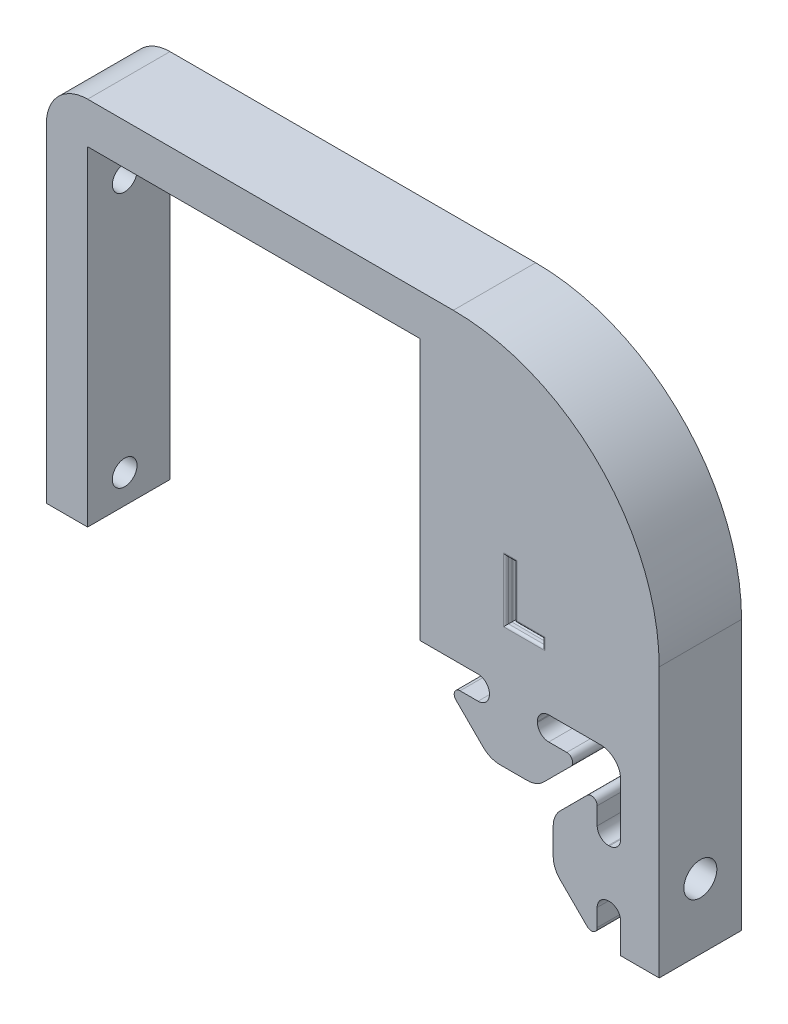
SolidWorks part; units mm, degrees
ref_plane "Front Plane" through (0, 0, 0) normal (0, 0, 1) x (1, 0, 0)
ref_plane "Top Plane" through (0, 0, 0) normal (0, 1, 0) x (1, 0, 0)
ref_plane "Right Plane" through (0, 0, 0) normal (1, 0, 0) x (0, 0, -1)
sketch "Sketch1" plane through (0, 0, 0) normal (0, 0, 1) x (1, 0, 0)
  line L0 (13.02, -7.9417) -> (17.7, -7.9417)
  line L1 (17.7, -7.9417) -> (17.7, 49.77)
  line L2 (17.7, 49.77) -> (-56.7, 49.77)
  line L3 (-14.4742, 2.77) -> (-67.0037, 2.77) construction
  line L4 (-19.4439, 2.77) -> (-19.4439, 44.77) construction
  line L5 (-10.5664, 13.02) -> (-10.5664, 44.77)
  line L6 (-10.5664, 44.77) -> (-51.7, 44.77)
  line L7 (-51.7, 44.77) -> (-51.7, 4.77)
  line L8 (-56.7, 49.77) -> (-56.7, 4.77)
  line L9 (-56.7, 4.77) -> (-51.7, 4.77)
  line L10 (12.7, -6.3331) -> (12.7, -7.9417) construction
  line L11 (13.02, -5.3171) -> (13.02, -4.2875)
  line L12 (11.651, -2.9185) -> (11.5392, -2.9185)
  line L13 (10.1702, -4.2875) -> (10.1702, -6.4021)
  line L14 (8.9631, -6.9029) -> (5.667, -3.6143)
  line L15 (4.8285, -1.5932) -> (4.8285, 1.5932)
  line L16 (5.667, 3.6143) -> (8.9631, 6.9029)
  line L17 (10.1702, 6.4021) -> (10.1702, 4.2875)
  line L18 (11.5392, 2.9185) -> (11.651, 2.9185)
  line L19 (13.02, 10.5773) -> (13.02, 4.2875)
  line L20 (6.3329, 13.02) -> (10.5626, 13.0198)
  line L22 (6.3329, 13.02) -> (4.2875, 13.02)
  line L23 (2.9185, 11.651) -> (2.9185, 11.5392)
  line L24 (4.2875, 10.1702) -> (6.4768, 10.1702)
  line L25 (6.981, 8.9509) -> (3.6723, 5.6497)
  line L26 (1.6558, 4.8158) -> (-1.6558, 4.8158)
  line L27 (-3.6723, 5.6497) -> (-6.981, 8.9509)
  line L28 (-6.4768, 10.1702) -> (-4.2875, 10.1702)
  line L29 (-2.9185, 11.5392) -> (-2.9185, 11.651)
  line L30 (-4.2875, 13.02) -> (-5.3171, 13.02)
  line L31 (-5.3171, 13.02) -> (-10.5664, 13.02)
  line L32 (13.02, -5.3171) -> (13.02, -7.9417)
  line L33 (13.02, -6.3331) -> (13.02, -7.9417) construction
  line L34 (13.02, 4.2875) -> (13.02, 5.3171) construction
  line L37 (5.3171, 13.02) -> (4.2875, 13.02) construction
  line L38 (-6.3331, 13.02) -> (-9.5504, 13.02) construction
  line L96 (12.7, -5.3171) -> (12.7, -4.2875) construction
  line L97 (11.651, -3.2385) -> (11.5392, -3.2385) construction
  line L98 (10.4902, -4.2875) -> (10.4902, -6.4021) construction
  line L99 (8.7371, -7.1294) -> (5.441, -3.8408) construction
  line L100 (4.5085, -1.5932) -> (4.5085, 1.5932) construction
  line L101 (5.441, 3.8408) -> (8.7371, 7.1294) construction
  line L102 (10.4902, 6.4021) -> (10.4902, 4.2875) construction
  line L103 (11.5392, 3.2385) -> (11.651, 3.2385) construction
  line L104 (12.7, 4.2875) -> (12.7, 5.3171) construction
  line L105 (12.7, 6.3331) -> (12.7, 9.5504) construction
  line L106 (9.5504, 12.7) -> (6.3331, 12.7) construction
  line L107 (5.3171, 12.7) -> (4.2875, 12.7) construction
  line L108 (3.2385, 11.651) -> (3.2385, 11.5392) construction
  line L109 (4.2875, 10.4902) -> (6.4768, 10.4902) construction
  line L110 (7.207, 8.7244) -> (3.8983, 5.4232) construction
  line L111 (1.6558, 4.4958) -> (-1.6558, 4.4958) construction
  line L112 (-3.8983, 5.4232) -> (-7.207, 8.7244) construction
  line L113 (-6.4768, 10.4902) -> (-4.2875, 10.4902) construction
  line L114 (-3.2385, 11.5392) -> (-3.2385, 11.651) construction
  line L115 (-4.2875, 12.7) -> (-5.3171, 12.7) construction
  line L116 (-6.3331, 12.7) -> (-9.5504, 12.7) construction
  arc A0 (13.02, -4.2875) -> (11.651, -2.9185) centre (11.651, -4.2875) ccw
  arc A1 (11.5392, -2.9185) -> (10.1702, -4.2875) centre (11.5392, -4.2875) ccw
  arc A2 (8.9631, -6.9029) -> (10.1702, -6.4021) centre (9.4628, -6.4021) ccw
  arc A3 (4.8285, -1.5932) -> (5.667, -3.6143) centre (7.6835, -1.5932) ccw
  arc A4 (5.667, 3.6143) -> (4.8285, 1.5932) centre (7.6835, 1.5932) ccw
  arc A5 (10.1702, 6.4021) -> (8.9631, 6.9029) centre (9.4628, 6.4021) ccw
  arc A6 (10.1702, 4.2875) -> (11.5392, 2.9185) centre (11.5392, 4.2875) ccw
  arc A7 (11.651, 2.9185) -> (13.02, 4.2875) centre (11.651, 4.2875) ccw
  arc A8 (4.2875, 13.02) -> (2.9185, 11.651) centre (4.2875, 11.651) ccw
  arc A9 (2.9185, 11.5392) -> (4.2875, 10.1702) centre (4.2875, 11.5392) ccw
  arc A10 (6.981, 8.9509) -> (6.4768, 10.1702) centre (6.4768, 9.4563) ccw
  arc A11 (1.6558, 4.8158) -> (3.6723, 5.6497) centre (1.6558, 7.6708) ccw
  arc A12 (-3.6723, 5.6497) -> (-1.6558, 4.8158) centre (-1.6558, 7.6708) ccw
  arc A13 (-6.4768, 10.1702) -> (-6.981, 8.9509) centre (-6.4768, 9.4563) ccw
  arc A14 (-4.2875, 10.1702) -> (-2.9185, 11.5392) centre (-4.2875, 11.5392) ccw
  arc A15 (-2.9185, 11.651) -> (-4.2875, 13.02) centre (-4.2875, 11.651) ccw
  arc A16 (13.02, 10.5773) -> (10.5626, 13.0198) centre (10.5918, 10.5918) ccw
  arc A17 (13.0198, 10.5625) -> (10.5626, 13.0198) centre (10.5918, 10.5918) ccw construction
  arc A114 (12.7, -5.3171) -> (12.7, -6.3331) centre (12.7, -5.8251) ccw construction
  arc A115 (12.7, -4.2875) -> (11.651, -3.2385) centre (11.651, -4.2875) ccw construction
  arc A116 (11.5392, -3.2385) -> (10.4902, -4.2875) centre (11.5392, -4.2875) ccw construction
  arc A117 (8.7371, -7.1294) -> (10.4902, -6.4021) centre (9.4628, -6.4021) ccw construction
  arc A118 (4.5085, -1.5932) -> (5.441, -3.8408) centre (7.6835, -1.5932) ccw construction
  arc A119 (5.441, 3.8408) -> (4.5085, 1.5932) centre (7.6835, 1.5932) ccw construction
  arc A120 (10.4902, 6.4021) -> (8.7371, 7.1294) centre (9.4628, 6.4021) ccw construction
  arc A121 (10.4902, 4.2875) -> (11.5392, 3.2385) centre (11.5392, 4.2875) ccw construction
  arc A122 (11.651, 3.2385) -> (12.7, 4.2875) centre (11.651, 4.2875) ccw construction
  arc A123 (12.7, 6.3331) -> (12.7, 5.3171) centre (12.7, 5.8251) ccw construction
  arc A124 (12.6998, 10.5664) -> (12.7, 9.5504) centre (12.7, 10.0584) ccw construction
  arc A125 (12.6998, 10.5664) -> (10.5664, 12.6998) centre (10.5918, 10.5918) ccw construction
  arc A126 (9.5504, 12.7) -> (10.5664, 12.6998) centre (10.0584, 12.7) ccw construction
  arc A127 (5.3171, 12.7) -> (6.3331, 12.7) centre (5.8251, 12.7) ccw construction
  arc A128 (4.2875, 12.7) -> (3.2385, 11.651) centre (4.2875, 11.651) ccw construction
  arc A129 (3.2385, 11.5392) -> (4.2875, 10.4902) centre (4.2875, 11.5392) ccw construction
  arc A130 (7.207, 8.7244) -> (6.4768, 10.4902) centre (6.4768, 9.4563) ccw construction
  arc A131 (1.6558, 4.4958) -> (3.8983, 5.4232) centre (1.6558, 7.6708) ccw construction
  arc A132 (-3.8983, 5.4232) -> (-1.6558, 4.4958) centre (-1.6558, 7.6708) ccw construction
  arc A133 (-6.4768, 10.4902) -> (-7.207, 8.7244) centre (-6.4768, 9.4563) ccw construction
  arc A134 (-4.2875, 10.4902) -> (-3.2385, 11.5392) centre (-4.2875, 11.5392) ccw construction
  arc A135 (-3.2385, 11.651) -> (-4.2875, 12.7) centre (-4.2875, 11.651) ccw construction
  arc A136 (-6.3331, 12.7) -> (-5.3171, 12.7) centre (-5.8251, 12.7) ccw construction
  arc A137 (-10.5664, 12.6998) -> (-9.5504, 12.7) centre (-10.0584, 12.7) ccw construction
  dimension "D1" = 47
  dimension "D2" = 74.4
  dimension "D3" = 5
  dimension "D4" = 5
  dimension "D5" = 40
  dimension "D6" = 5
  dimension "D8" = 0.32
  dimension "D7" = 6.2898
  dimension "D9" = 4.2297
  dimension "D11" = 57.7117
extrude "Boss-Extrude1" add sketch "Sketch1" along normal blind 10
sketch "Sketch2" plane through (-56.7, 0, 0) normal (-1, 0, 0) x (0, 0, 1)
  line L1 (10, 49.77) -> (0, 49.77) construction
  line L2 (10, 29.3002) -> (10, 4.77) construction
  line L7 (5.5, 39.27) -> (5.5, 8.27) construction
  circle A0 centre (5.5, 8.27) radius 1.5
  circle A1 centre (5.5, 39.27) radius 1.5
  dimension "D3" = 3
  dimension "D4" = 3
  dimension "D1" = 4.5
  dimension "D2" = 31
  dimension "D5" = 10.5
extrude "Cut-Extrude1" cut sketch "Sketch2" against normal up to next
fillet "Fillet3" radius 5 1 edges at (-56.7, 49.77, 5)
sketch "Sketch3" plane through (17.7, 0, 0) normal (1, 0, 0) x (0, 0, -1)
  line L0 (-5, 1.5932) -> (-5, -1.5932) construction
  line L1 (-10, 0) -> (0, 0) construction
  line L4 (0, -1.5932) -> (0, 1.5932)
  line L5 (-10, -1.5932) -> (0, -1.5932)
  line L6 (-10, 1.5932) -> (-10, -1.5932)
  line L7 (0, 1.5932) -> (-10, 1.5932)
  line L12 (0, -1.5932) -> (0, 1.5932) construction
  line L13 (-10, -1.5932) -> (0, -1.5932) construction
  line L14 (-10, 1.5932) -> (-10, -1.5932) construction
  line L15 (0, 1.5932) -> (-10, 1.5932) construction
  circle A2 centre (-5, 0) radius 2
  dimension "D1" = 0
extrude "Cut-Extrude2" cut sketch "Sketch3" against normal up to next contours A2
fillet "Fillet4" radius 25 1 edges at (17.7, 49.77, 5)
sketch "Sketch7" plane through (0, 0, 10) normal (0, 0, 1) x (1, 0, 0)
  text T0 "L" font "Arial" height in points 28
extrude "Cut-Extrude7" cut sketch "Sketch7" against normal blind 1
fillet "Fillet8" radius 0.3 12 edges at (-0.901, 23.4386, 9) (-0.3939, 27.0343, 9) (0.1132, 23.8535, 9) (1.8188, 20.6728, 9) (3.5244, 20.2579, 9) (1.3117, 19.843, 9) (1.3117, 19.843, 10) (3.5244, 20.2579, 10) (1.8188, 20.6728, 10) (0.1132, 23.8535, 10) (-0.3939, 27.0343, 10) (-0.901, 23.4386, 10)
sketch "Sketch8" plane through (-10.5664, 0, 0) normal (-1, 0, 0) x (0, 0, 1)
  line L4 (0, 44.77) -> (0, 13.02)
  line L5 (0, 13.02) -> (10, 13.02)
  line L6 (10, 13.02) -> (10, 44.77)
  line L7 (10, 44.77) -> (0, 44.77)
  line L8 (0, 44.77) -> (0, 13.02)
  line L9 (0, 13.02) -> (10, 13.02)
  line L10 (10, 13.02) -> (10, 44.77)
  line L11 (10, 44.77) -> (0, 44.77)
  dimension "D1" = 0
extrude "Boss-Extrude2" add sketch "Sketch8" along normal blind 0.8
